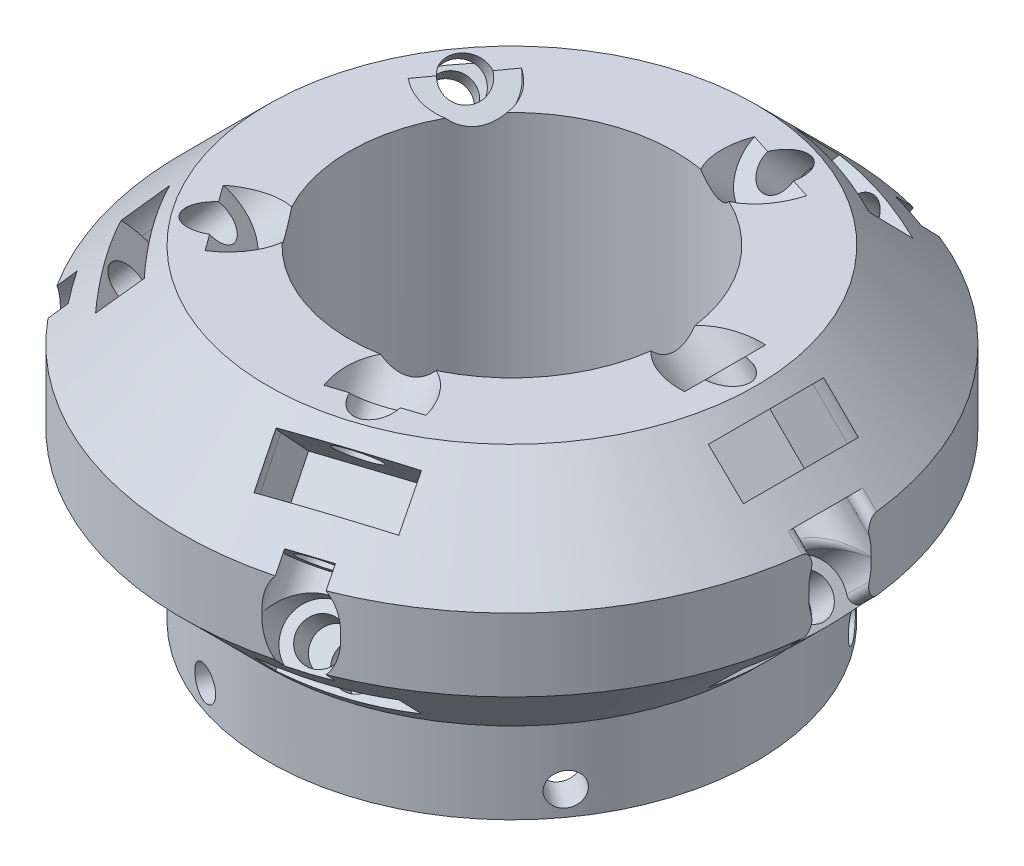
SolidWorks part; units mm, degrees
ref_plane "Front Plane" through (0, 0, 0) normal (0, 0, 1) x (1, 0, 0)
ref_plane "Top Plane" through (0, 0, 0) normal (0, 1, 0) x (1, 0, 0)
ref_plane "Right Plane" through (0, 0, 0) normal (1, 0, 0) x (0, 0, -1)
sketch "Sketch1" plane through (0, 0, 0) normal (0, 0, 1) x (1, 0, 0)
  line L0 (0, 0) -> (20, 0) construction
  line L1 (20, 15) -> (20, -15)
  line L2 (20, -15) -> (30, -15)
  line L3 (30, -15) -> (40.5355, -4.4645)
  line L4 (40.5355, -4.4645) -> (40.5355, 4.4645)
  line L5 (32, -13) -> (24.9289, -5.9289) construction
  line L6 (24.9289, -5.9289) -> (28.4645, -2.3934) construction
  line L7 (28.4645, -2.3934) -> (35.5355, -9.4645) construction
  line L8 (29.8787, -10.8787) -> (33.4142, -7.3431) construction
  line L9 (55, 0) -> (-55, 0) construction
  line L10 (29.8787, 10.8787) -> (33.4142, 7.3431) construction
  line L11 (28.4645, 2.3934) -> (35.5355, 9.4645) construction
  line L12 (24.9289, 5.9289) -> (28.4645, 2.3934) construction
  line L13 (32, 13) -> (24.9289, 5.9289) construction
  line L14 (30, 15) -> (40.5355, 4.4645)
  line L15 (20, 15) -> (30, 15)
  line L16 (0, 0) -> (0, 15) construction
  point P13 (0, 0)
  point P30 (40.5355, 0)
  dimension "D1" = 20
  dimension "D2" = 10
  dimension "D3" = 5
  dimension "D4" = 7
  dimension "D5" = 2
  dimension "D6" = 45
  dimension "D7" = 5
  dimension "D8" = 10
  dimension "D9" = 15
ref_plane "Plane1" through (13.0355, 13.0355, 0) normal (-0.7071, -0.7071, 0) x (-0.7071, 0.7071, 0)
sketch "Sketch4" plane through (13.0355, 13.0355, 0) normal (-0.7071, -0.7071, 0) x (-0.7071, 0.7071, 0)
  line L0 (-28.8198, 7.5) -> (-21.3198, 7.5)
  line L1 (-21.3198, 7.5) -> (-21.3198, -7.5)
  line L2 (-21.3198, -7.5) -> (-28.8198, -7.5)
  arc A0 (-28.8198, 7.5) -> (-28.8198, -7.5) centre (-28.8198, 0) ccw
  circle A1 centre (-28.8198, 0) radius 2.5
  point P0 (-28.8198, 0)
  dimension "D1" = 15
  dimension "D2" = 5
revolve "Revolve2" add sketch "Sketch1" angle 360 about L16
sketch "Sketch7" plane through (0, -15, 0) normal (0, -1, 0) x (1, 0, 0)
  circle A0 centre (0, 0) radius 30
  circle A1 centre (0, 0) radius 20
extrude "Boss-Extrude1" add sketch "Sketch7" along normal blind 10
extrude "Cut-Extrude1" cut sketch "Sketch4" along normal blind 5.5 and the other way blind 0.5
extrude "Cut-Extrude2" cut sketch "Sketch4<2>" against normal through all both and the other way through all contours A1
sketch "Sketch4<2>" plane through (13.0355, 13.0355, 0) normal (-0.7071, -0.7071, 0) x (-0.7071, 0.7071, 0) same geometry as "Sketch4"
sketch "Sketch5" plane through (9.1464, 9.1464, 0) normal (0.7071, 0.7071, 0) x (0, 0, -1)
  circle A0 centre (0, -28.8198) radius 5
  dimension "D1" = 10
extrude "Cut-Extrude3" cut sketch "Sketch5" against normal blind 15 from offset 5 offset against normal yes
sketch "Sketch6" plane through (13.3891, 13.3891, 0) normal (-0.7071, -0.7071, 0) x (0, 0, 1)
  circle A0 centre (0, -28.8198) radius 3.85
  dimension "D1" = 7.7
extrude "Cut-Extrude4" cut sketch "Sketch6" against normal through all from offset 4 offset against normal yes
mirror "Mirror1" about plane through (0, 0, 0) normal (0, 1, 0) of "Cut-Extrude4", "Cut-Extrude3", "Cut-Extrude1", "Cut-Extrude2"
fillet "Fillet1" radius 1 5 edges at (35.3126, 0, 0)
ref_axis "Axis1" through (0, 17.1313, 0) along (0, -1, 0)
pattern_circular "CirPattern2" count 5 over 360 about axis through (0, 17.1313, 0) along (0, -1, 0) of "Mirror1"
chamfer "Chamfer1" distance 7 angle 45 1 edges at (-6.1803, -25, -19.0211)
sketch "Sketch10" plane through (0, 0, 0) normal (1, 0, 0) x (0, 0, -1)
  line L0 (0, -25) -> (0, -22) construction
  line L1 (-30, -25) -> (30, -25) construction
  circle A0 centre (0, -22) radius 2
  dimension "D2" = 4
  dimension "D1" = 3
extrude "Cut-Extrude5" cut sketch "Sketch10" against normal through all
sketch "Sketch11" plane through (0, 0, 0) normal (1, 0, 0) x (0, 0, -1)
  line L0 (3.25, -22) -> (3.25, -25.8274)
  line L1 (3.25, -25.8274) -> (-3.25, -25.8274)
  line L2 (-3.25, -25.8274) -> (-3.25, -22)
  arc A0 (3.25, -22) -> (-3.25, -22) centre (0, -22) ccw
  dimension "D1" = 6.5
extrude "Cut-Extrude6" cut sketch "Sketch11" against normal blind 26
pattern_circular "CirPattern4" count 5 over 360 about axis through (0, 17.1313, 0) along (0, -1, 0) of "Cut-Extrude6", "Cut-Extrude5"
